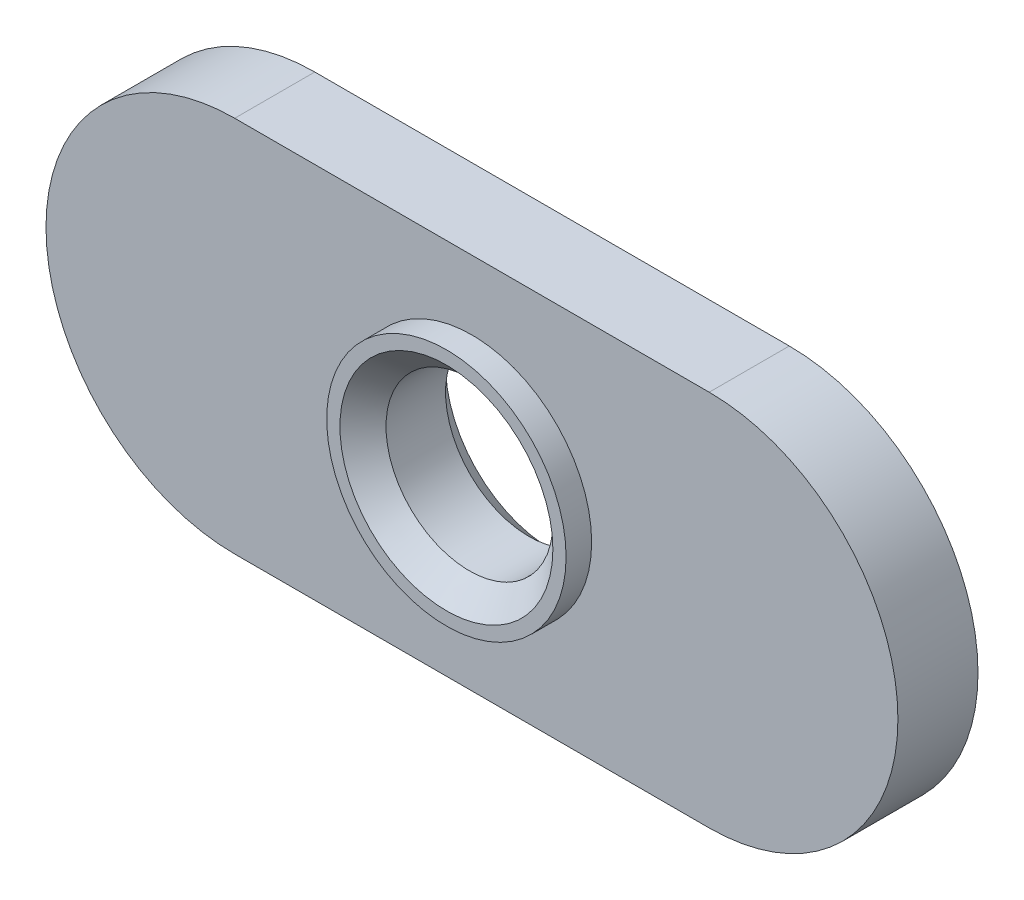
SolidWorks part; units mm, degrees
ref_plane "Front Plane" through (0, 0, 0) normal (0, 0, 1) x (1, 0, 0)
ref_plane "Top Plane" through (0, 0, 0) normal (0, 1, 0) x (1, 0, 0)
ref_plane "Right Plane" through (0, 0, 0) normal (1, 0, 0) x (0, 0, -1)
ref_plane "Plane1" through (0, 0, 0) normal (0, 0, 1) x (1, 0, 0)
sketch "Sketch1" plane through (0, 0, 0) normal (0, 0, 1) x (1, 0, 0)
  line L0 (-7.0739, -5.6261) -> (7.0739, -5.6261)
  line L1 (7.0739, 5.6261) -> (-7.0739, 5.6261)
  arc A0 (-7.0739, 5.6261) -> (-7.0739, -5.6261) centre (-7.0739, 0) ccw
  arc A1 (7.0739, -5.6261) -> (7.0739, 5.6261) centre (7.0739, 0) ccw
extrude "Boss-Extrude1" add sketch "Sketch1" against normal blind 1.1938 and the other way blind 1.1938
ref_plane "Plane2" through (0, 0, 0) normal (0, 0, 1) x (1, 0, 0)
sketch "Sketch2" plane through (0, 0, 0) normal (0, 0, 1) x (1, 0, 0)
  circle A0 centre (0, 0) radius 3.5687
extrude "Boss-Extrude2" add sketch "Sketch2" along normal blind 1.9558
ref_plane "Plane3" through (0, 0, 0) normal (1, 0, 0) x (0, 0, -1)
sketch "Sketch3" plane through (0, 0, 0) normal (1, 0, 0) x (0, 0, -1)
  line L0 (-1.9558, 0) -> (-1.9558, 3.175)
  line L1 (-1.9558, 3.175) -> (-1.2687, 2.4879)
  line L2 (-1.2687, 2.4879) -> (0.5067, 2.4879)
  line L3 (0.5067, 2.4879) -> (1.1938, 3.175)
  line L4 (1.1938, 3.175) -> (1.1938, 0)
  line L5 (1.1938, 0) -> (-1.9558, 0)
  line L6 (1.1938, 0) -> (-1.9558, 0) construction
revolve "Cut-Revolve1" cut sketch "Sketch3" angle 360 about L6 reverse direction yes
